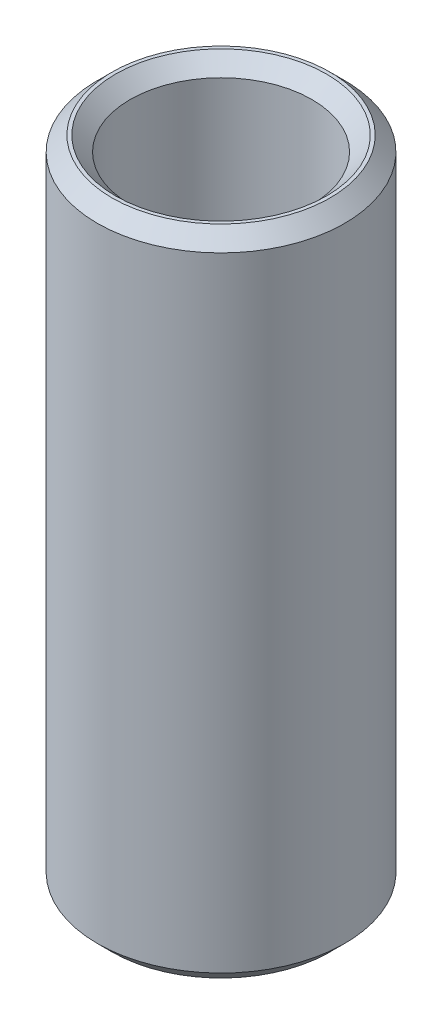
SolidWorks part; units mm, degrees
ref_plane "Front Plane" through (0, 0, 0) normal (0, 0, 1) x (1, 0, 0)
ref_plane "Top Plane" through (0, 0, 0) normal (0, 1, 0) x (1, 0, 0)
ref_plane "Right Plane" through (0, 0, 0) normal (1, 0, 0) x (0, 0, -1)
sketch "Sketch1" plane through (0, 0, 0) normal (0, 1, 0) x (1, 0, 0)
  circle A0 centre (0, 0) radius 10
  dimension "SLEEVE_OD" = 20
extrude "Boss-Extrude1" add sketch "Sketch1" along normal blind 52.7964
sketch "Sketch2" plane through (0, 0, 0) normal (0, 1, 0) x (1, 0, 0)
  circle A0 centre (0, 0) radius 7.3483
  dimension "BORE_D" = 14.6967
extrude "Cut-Extrude1" cut sketch "Sketch2" along normal through all
chamfer "Chamfer1" distance 1.1857 angle 45 4 edges at (0, 52.7964, 7.3483) (0, 0, 7.3483) (0, 0, 10) (0, 52.7964, 10)
